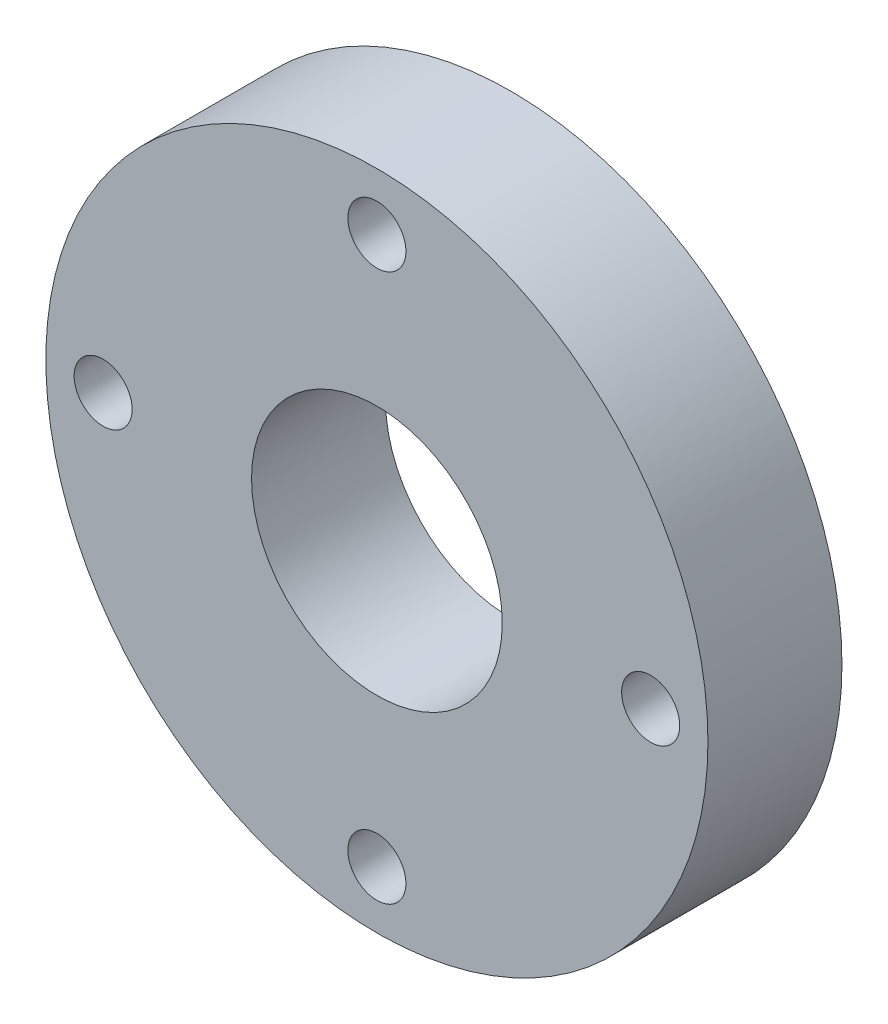
SolidWorks part; units mm, degrees
material "6061-T6 (SS)"
ref_plane "Front Plane" through (0, 0, 0) normal (0, 0, 1) x (1, 0, 0)
ref_plane "Top Plane" through (0, 0, 0) normal (0, 1, 0) x (1, 0, 0)
ref_plane "Right Plane" through (0, 0, 0) normal (1, 0, 0) x (0, 0, -1)
sketch "Sketch1" plane through (0, 0, 0) normal (1, 0, 0) x (0, 0, -1)
  line L0 (-95.847, -9.525) -> (-140.95, -9.525)
  line L5 (-1000, 0) -> (49000, 0)
  line L6 (0, -9.525) -> (0, 9.525)
  line L13 (0, 9.525) -> (-45.847, 9.525)
  line L26 (-45.847, 9.525) -> (-45.847, 14)
  line L27 (-45.847, 14) -> (-95.847, 14)
  line L32 (-95.847, 14) -> (-95.847, 9.525)
  line L34 (-160, 7) -> (-160, -7)
  line L36 (-95.847, -9.525) -> (-95.847, -14)
  line L37 (-95.847, -14) -> (-45.847, -14)
  line L38 (-45.847, -14) -> (-45.847, -9.525)
  line L39 (0, -9.525) -> (-45.847, -9.525)
  line L40 (-25.305, 37.6491) -> (-16.305, 37.6491)
  line L41 (-111.341, 22.6187) -> (-95.847, 22.6187)
  line L42 (-111.341, 22.6187) -> (-111.341, -22.6187)
  line L43 (-111.341, -22.6187) -> (-95.847, -22.6187)
  line L44 (-95.847, 22.6187) -> (-95.847, -22.6187)
  line L45 (-111.341, 22.6187) -> (-95.847, -22.6187) construction
  line L46 (-111.341, -22.6187) -> (-95.847, 22.6187) construction
  line L47 (-30.353, 22.6187) -> (-45.847, 22.6187)
  line L48 (-30.353, 22.6187) -> (-30.353, -22.6187)
  line L49 (-30.353, -22.6187) -> (-45.847, -22.6187)
  line L50 (-45.847, 22.6187) -> (-45.847, -22.6187)
  line L51 (-30.353, 22.6187) -> (-45.847, -22.6187) construction
  line L52 (-30.353, -22.6187) -> (-45.847, 22.6187) construction
  line L59 (-16.305, 37.6491) -> (-16.305, -37.6491)
  line L60 (-16.305, -37.6491) -> (-25.305, -37.6491)
  line L61 (-25.305, -22.6187) -> (-27.305, -22.6187)
  line L62 (-27.305, -22.6187) -> (-27.305, -12.5)
  line L63 (-27.305, -12.5) -> (-25.305, -12.5)
  line L64 (-25.305, -12.5) -> (-25.305, 12.5)
  line L65 (-25.305, 12.5) -> (-27.305, 12.5)
  line L66 (-27.305, 12.5) -> (-27.305, 22.6187)
  line L67 (-27.305, 22.6187) -> (-25.305, 22.6187)
  line L68 (-25.305, 22.6187) -> (-25.305, 37.6491)
  line L69 (-25.305, -22.6187) -> (-25.305, -37.6491)
  line L71 (-119.469, 37.6491) -> (-26.305, 37.6491)
  line L72 (-119.469, 37.6491) -> (-119.469, -37.6491)
  line L73 (-119.469, -37.6491) -> (-26.305, -37.6491)
  line L74 (-26.305, 37.6491) -> (-26.305, -37.6491)
  line L75 (-119.469, 37.6491) -> (-26.305, -37.6491) construction
  line L76 (-119.469, -37.6491) -> (-26.305, 37.6491) construction
  line L77 (-140.95, -9.525) -> (-140.95, -7)
  line L78 (-140.95, -7) -> (-160, -7)
  line L79 (-95.847, 9.525) -> (-140.95, 9.525)
  line L80 (-140.95, 7) -> (-160, 7)
  line L81 (-140.95, 9.525) -> (-140.95, 7)
  line L82 (-118.3985, 9.525) -> (-118.3985, -9.525) construction
  line L83 (-22.9235, 9.525) -> (-22.9235, -9.525) construction
  line L96 (-119.469, 37.6492) -> (-134.709, 37.6492)
  line L98 (-119.469, -37.6491) -> (-134.709, -37.6491)
  line L99 (-134.709, 37.6492) -> (-134.709, -37.6491)
  line L110 (-119.469, 37.6492) -> (-119.469, -37.6491)
  point P3 (0, 0)
  point P18 (-103.594, 0)
  point P24 (-38.1, 0)
  point P29 (-72.887, 0)
  point P48 (-16.305, 31.1339)
  point P58 (0, 0)
  point P59 (0, 0)
  point P70 (-134.709, 31.1339)
revolve "Main_body" add sketch "Sketch1" angle 360 about L5 region at (0, 23.5871, 127.089)
sketch "Sketch5" plane through (0, 0, 134.709) normal (0, 0, 1) x (1, 0, 0)
  circle A0 centre (0, 0) radius 14.2558
  dimension "D1" = 28.5115
extrude "seal_seat" cut sketch "Sketch5" against normal through all
hole_wizard "M6 Clearance Hole1" positions "Sketch3" profile "Sketch4" hole size "M6" standard "ANSI Metric" end condition through all
sketch "Sketch3" plane through (0, 0, 134.709) normal (0, 0, 1) x (1, 0, 0)
  point P0 (0, 31.1339)
sketch "Sketch4" plane through (0, 31.1339, 134.709) normal (1, 0, 0) x (0, -1, 0)
  line L0 (0, 0) -> (0, 15.24)
  line L1 (0, 15.24) -> (3.3, 15.24)
  line L2 (3.3, 15.24) -> (3.3, 0)
  line L5 (3.3, 0) -> (0, 0)
  line L11 (0, -6.35) -> (0, 107.95) construction
  dimension "Thru Hole Dia." = 6.6
  dimension "Thru Hole Depth" = 15.24
pattern_circular "CirPattern1" count 4 over 360 about axis through (0, 0, 1000) along (0, 0, -1) of "M6 Clearance Hole1"
